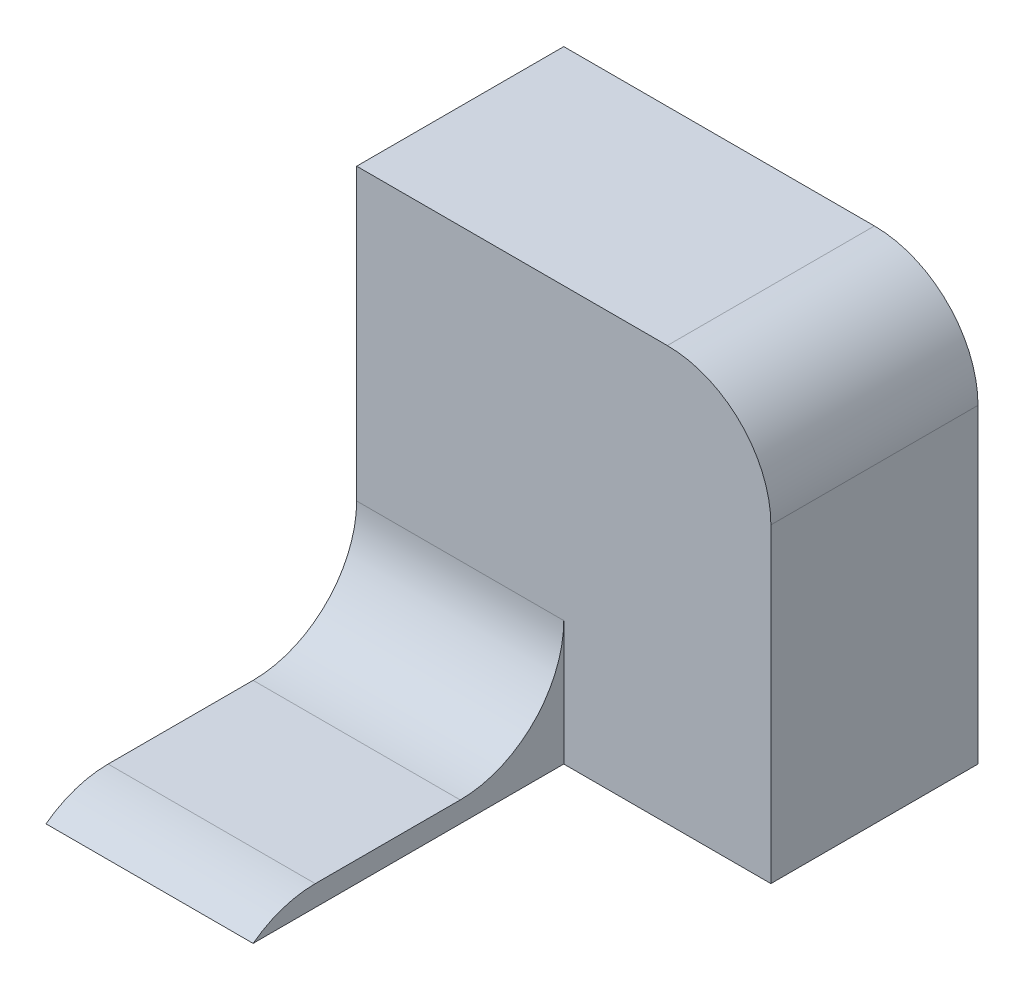
SolidWorks part; units mm, degrees
ref_plane "Front Plane" through (0, 0, 0) normal (0, 0, 1) x (1, 0, 0)
ref_plane "Top Plane" through (0, 0, 0) normal (0, 1, 0) x (1, 0, 0)
ref_plane "Right Plane" through (0, 0, 0) normal (1, 0, 0) x (0, 0, -1)
sketch "Sketch1" plane through (0, 0, 0) normal (0, 0, 1) x (1, 0, 0)
  line L1 (-30, -2) -> (-10, -2)
  line L2 (-10, -2) -> (-10, 0)
  line L3 (-10, 0) -> (-30, 0)
  line L4 (-30, 0) -> (-30, -2)
  dimension "D1" = 20
  dimension "Width" = 2
extrude "Boss-Extrude1" add sketch "Sketch1" along normal blind 30
sketch "Sketch2" plane through (0, 0, 0) normal (0, 0, 1) x (1, 0, 0)
  line L1 (-30, -2) -> (10, -2)
  line L2 (10, -2) -> (10, 38)
  line L3 (10, 38) -> (-30, 38)
  line L4 (-30, 38) -> (-30, -2)
  dimension "D1" = 40
  dimension "Width" = 40
extrude "Boss-Extrude2" add sketch "Sketch2" against normal blind 20
fillet "Fillet1" radius 10 3 edges at (-20, 0, 0) (10, 38, -10) (-20, 0, 30)
